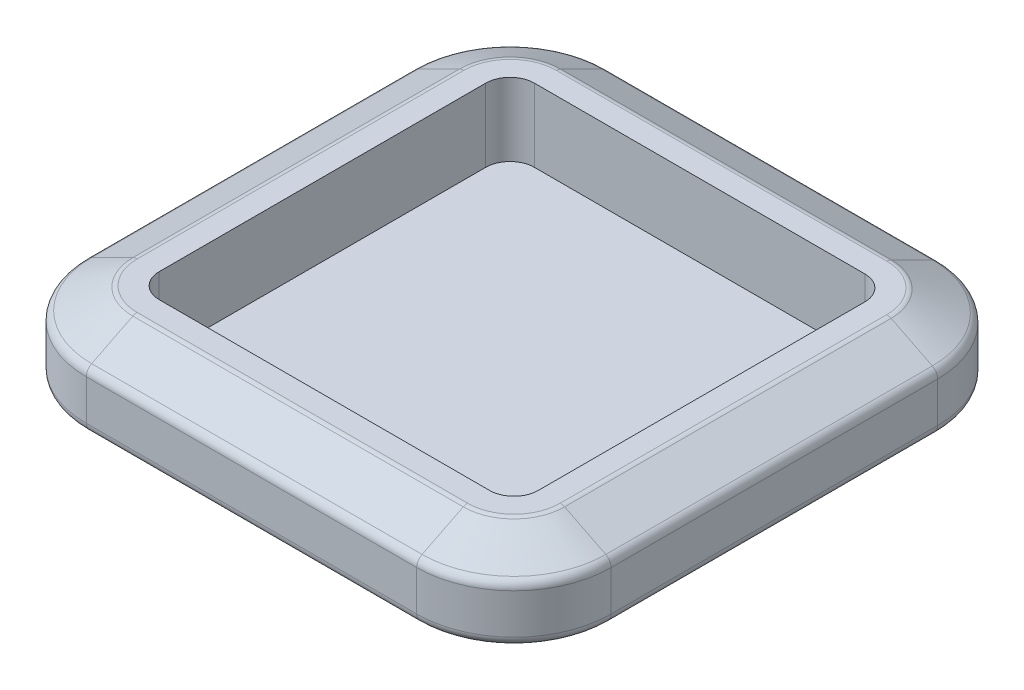
SolidWorks part; units mm, degrees
ref_plane "Front Plane" through (0, 0, 0) normal (0, 0, 1) x (1, 0, 0)
ref_plane "Top Plane" through (0, 0, 0) normal (0, 1, 0) x (1, 0, 0)
ref_plane "Right Plane" through (0, 0, 0) normal (1, 0, 0) x (0, 0, -1)
sketch "Sketch3" plane through (0, 0, 0) normal (0, 1, 0) x (1, 0, 0)
  line L0 (76.5438, 73.5629) -> (76.5438, 2.863)
  line L1 (73.5438, -0.137) -> (2.8437, -0.137)
  line L2 (-0.1563, 2.863) -> (-0.1563, 73.5629)
  line L3 (2.8437, 76.5629) -> (73.5438, 76.5629)
  line L4 (16.6192, 59.7877) -> (16.6192, 60.3885)
  line L5 (16.6192, 60.3885) -> (17.4184, 60.3885)
  line L6 (17.4184, 60.3885) -> (17.4184, 73.1876)
  line L7 (17.4184, 73.1876) -> (16.6192, 73.1876)
  line L8 (16.6192, 73.1876) -> (16.6192, 73.7884)
  line L9 (16.6192, 73.7884) -> (2.6183, 73.7884)
  line L10 (2.6183, 73.7884) -> (2.6183, 73.1876)
  line L11 (2.6183, 73.1876) -> (1.819, 73.1876)
  line L12 (1.819, 73.1876) -> (1.819, 60.3885)
  line L13 (1.819, 60.3885) -> (2.6183, 60.3885)
  line L14 (2.6183, 60.3885) -> (2.6183, 59.7877)
  line L15 (2.6183, 59.7877) -> (16.6192, 59.7877)
  line L16 (16.6192, 21.6876) -> (16.6192, 22.2884)
  line L17 (16.6192, 22.2884) -> (17.4184, 22.2884)
  line L18 (17.4184, 22.2884) -> (17.4184, 35.0876)
  line L19 (17.4184, 35.0876) -> (16.6192, 35.0876)
  line L20 (16.6192, 35.0876) -> (16.6192, 35.6884)
  line L21 (16.6192, 35.6884) -> (2.6183, 35.6884)
  line L22 (2.6183, 35.6884) -> (2.6183, 35.0876)
  line L23 (2.6183, 35.0876) -> (1.819, 35.0876)
  line L24 (1.819, 35.0876) -> (1.819, 22.2884)
  line L25 (1.819, 22.2884) -> (2.6183, 22.2884)
  line L26 (2.6183, 22.2884) -> (2.6183, 21.6876)
  line L27 (2.6183, 21.6876) -> (16.6192, 21.6876)
  line L28 (35.669, 59.7877) -> (35.669, 60.3885)
  line L29 (35.669, 60.3885) -> (36.4684, 60.3885)
  line L30 (36.4684, 60.3885) -> (36.4684, 73.1876)
  line L31 (36.4684, 73.1876) -> (35.669, 73.1876)
  line L32 (35.669, 73.1876) -> (35.669, 73.7884)
  line L33 (35.669, 73.7884) -> (21.6683, 73.7884)
  line L34 (21.6683, 73.7884) -> (21.6683, 73.1876)
  line L35 (21.6683, 73.1876) -> (20.869, 73.1876)
  line L36 (20.869, 73.1876) -> (20.869, 60.3885)
  line L37 (20.869, 60.3885) -> (21.6683, 60.3885)
  line L38 (21.6683, 60.3885) -> (21.6683, 59.7877)
  line L39 (21.6683, 59.7877) -> (35.669, 59.7877)
  line L40 (35.669, 40.7377) -> (35.669, 41.3385)
  line L41 (35.669, 41.3385) -> (36.4684, 41.3385)
  line L42 (36.4684, 41.3385) -> (36.4684, 54.1376)
  line L43 (36.4684, 54.1376) -> (35.669, 54.1376)
  line L44 (35.669, 54.1376) -> (35.669, 54.7384)
  line L45 (35.669, 54.7384) -> (21.6683, 54.7384)
  line L46 (21.6683, 54.7384) -> (21.6683, 54.1376)
  line L47 (21.6683, 54.1376) -> (20.869, 54.1376)
  line L48 (20.869, 54.1376) -> (20.869, 41.3385)
  line L49 (20.869, 41.3385) -> (21.6683, 41.3385)
  line L50 (21.6683, 41.3385) -> (21.6683, 40.7377)
  line L51 (21.6683, 40.7377) -> (35.669, 40.7377)
  line L52 (35.669, 21.6876) -> (35.669, 22.2884)
  line L53 (35.669, 22.2884) -> (36.4684, 22.2884)
  line L54 (36.4684, 22.2884) -> (36.4684, 35.0876)
  line L55 (36.4684, 35.0876) -> (35.669, 35.0876)
  line L56 (35.669, 35.0876) -> (35.669, 35.6884)
  line L57 (35.669, 35.6884) -> (21.6683, 35.6884)
  line L58 (21.6683, 35.6884) -> (21.6683, 35.0876)
  line L59 (21.6683, 35.0876) -> (20.869, 35.0876)
  line L60 (20.869, 35.0876) -> (20.869, 22.2884)
  line L61 (20.869, 22.2884) -> (21.6683, 22.2884)
  line L62 (21.6683, 22.2884) -> (21.6683, 21.6876)
  line L63 (21.6683, 21.6876) -> (35.669, 21.6876)
  line L64 (54.719, 59.7877) -> (54.719, 60.3885)
  line L65 (54.719, 60.3885) -> (55.5184, 60.3885)
  line L66 (55.5184, 60.3885) -> (55.5184, 73.1876)
  line L67 (55.5184, 73.1876) -> (54.719, 73.1876)
  line L68 (54.719, 73.1876) -> (54.719, 73.7884)
  line L69 (54.719, 73.7884) -> (40.7183, 73.7884)
  line L70 (40.7183, 73.7884) -> (40.7183, 73.1876)
  line L71 (40.7183, 73.1876) -> (39.9189, 73.1876)
  line L72 (39.9189, 73.1876) -> (39.9189, 60.3885)
  line L73 (39.9189, 60.3885) -> (40.7183, 60.3885)
  line L74 (40.7183, 60.3885) -> (40.7183, 59.7877)
  line L75 (40.7183, 59.7877) -> (54.719, 59.7877)
  line L76 (54.719, 40.7377) -> (54.719, 41.3385)
  line L77 (54.719, 41.3385) -> (55.5184, 41.3385)
  line L78 (55.5184, 41.3385) -> (55.5184, 54.1376)
  line L79 (55.5184, 54.1376) -> (54.719, 54.1376)
  line L80 (54.719, 54.1376) -> (54.719, 54.7384)
  line L81 (54.719, 54.7384) -> (40.7183, 54.7384)
  line L82 (40.7183, 54.7384) -> (40.7183, 54.1376)
  line L83 (40.7183, 54.1376) -> (39.9189, 54.1376)
  line L84 (39.9189, 54.1376) -> (39.9189, 41.3385)
  line L85 (39.9189, 41.3385) -> (40.7183, 41.3385)
  line L86 (40.7183, 41.3385) -> (40.7183, 40.7377)
  line L87 (40.7183, 40.7377) -> (54.719, 40.7377)
  line L88 (54.719, 21.6876) -> (54.719, 22.2884)
  line L89 (54.719, 22.2884) -> (55.5184, 22.2884)
  line L90 (55.5184, 22.2884) -> (55.5184, 35.0876)
  line L91 (55.5184, 35.0876) -> (54.719, 35.0876)
  line L92 (54.719, 35.0876) -> (54.719, 35.6884)
  line L93 (54.719, 35.6884) -> (40.7183, 35.6884)
  line L94 (40.7183, 35.6884) -> (40.7183, 35.0876)
  line L95 (40.7183, 35.0876) -> (39.9189, 35.0876)
  line L96 (39.9189, 35.0876) -> (39.9189, 22.2884)
  line L97 (39.9189, 22.2884) -> (40.7183, 22.2884)
  line L98 (40.7183, 22.2884) -> (40.7183, 21.6876)
  line L99 (40.7183, 21.6876) -> (54.719, 21.6876)
  line L100 (54.719, 2.6376) -> (54.719, 3.2384)
  line L101 (54.719, 3.2384) -> (55.5184, 3.2384)
  line L102 (55.5184, 3.2384) -> (55.5184, 16.0376)
  line L103 (55.5184, 16.0376) -> (54.719, 16.0376)
  line L104 (54.719, 16.0376) -> (54.719, 16.6384)
  line L105 (54.719, 16.6384) -> (40.7183, 16.6384)
  line L106 (40.7183, 16.6384) -> (40.7183, 16.0376)
  line L107 (40.7183, 16.0376) -> (39.9189, 16.0376)
  line L108 (39.9189, 16.0376) -> (39.9189, 3.2384)
  line L109 (39.9189, 3.2384) -> (40.7183, 3.2384)
  line L110 (40.7183, 3.2384) -> (40.7183, 2.6376)
  line L111 (40.7183, 2.6376) -> (54.719, 2.6376)
  line L112 (4.8812, 17.3884) -> (4.8812, 19.1629)
  line L113 (3.4438, 17.0648) -> (3.4438, 16.6384)
  line L114 (3.4438, 16.6384) -> (2.6177, 16.6384)
  line L115 (2.6177, 16.6384) -> (2.6177, 16.0374)
  line L116 (2.6177, 16.0374) -> (1.8187, 16.0374)
  line L117 (1.8187, 16.0374) -> (1.8187, 3.2386)
  line L118 (1.8187, 3.2386) -> (2.6177, 3.2386)
  line L119 (2.6177, 3.2386) -> (2.6177, 2.6376)
  line L120 (2.6177, 2.6376) -> (35.6687, 2.6376)
  line L121 (35.6687, 2.6376) -> (35.6687, 3.2386)
  line L122 (35.6687, 3.2386) -> (36.4677, 3.2386)
  line L123 (36.4677, 3.2386) -> (36.4677, 16.0374)
  line L124 (36.4677, 16.0374) -> (35.6687, 16.0374)
  line L125 (35.6687, 16.0374) -> (35.6687, 16.6384)
  line L126 (35.6687, 16.6384) -> (34.8436, 16.6384)
  line L127 (34.8436, 16.6384) -> (34.8436, 17.3884)
  line L128 (34.8436, 17.3884) -> (27.3432, 17.3884)
  line L129 (27.3432, 17.3884) -> (27.3432, 16.6384)
  line L130 (27.3432, 16.6384) -> (10.9442, 16.6384)
  line L131 (10.9442, 16.6384) -> (10.9442, 17.3884)
  line L132 (10.9442, 17.3884) -> (4.8812, 17.3884)
  line L133 (3.6353, 54.7384) -> (3.6353, 55.0694)
  line L134 (2.6183, 54.8329) -> (2.6183, 54.7384)
  line L135 (2.6183, 54.7384) -> (2.6183, 54.1376)
  line L136 (2.6183, 54.1376) -> (1.819, 54.1376)
  line L137 (1.819, 54.1376) -> (1.819, 41.3385)
  line L138 (1.819, 41.3385) -> (2.6183, 41.3385)
  line L139 (2.6183, 41.3385) -> (2.6183, 40.7377)
  line L140 (2.6183, 40.7377) -> (16.6192, 40.7377)
  line L141 (16.6192, 40.7377) -> (16.6192, 41.3385)
  line L142 (16.6192, 41.3385) -> (17.4184, 41.3385)
  line L143 (17.4184, 41.3385) -> (17.4184, 54.1376)
  line L144 (17.4184, 54.1376) -> (16.6192, 54.1376)
  line L145 (16.6192, 54.1376) -> (16.6192, 54.7384)
  line L146 (16.6192, 54.7384) -> (3.6353, 54.7384)
  line L147 (59.0183, 27.3624) -> (59.7683, 27.3624)
  line L148 (59.7683, 27.3624) -> (59.7683, 10.9635)
  line L149 (59.7683, 10.9635) -> (59.0183, 10.9635)
  line L150 (59.0183, 10.9635) -> (59.0183, 3.4631)
  line L151 (59.0183, 3.4631) -> (59.7683, 3.4631)
  line L152 (59.7683, 3.4631) -> (59.7683, 2.6379)
  line L153 (59.7683, 2.6379) -> (60.3693, 2.6379)
  line L154 (60.3693, 2.6379) -> (60.3693, 1.8389)
  line L155 (60.3693, 1.8389) -> (73.168, 1.8389)
  line L156 (73.168, 1.8389) -> (73.168, 2.6379)
  line L157 (73.168, 2.6379) -> (73.769, 2.6379)
  line L158 (73.769, 2.6379) -> (73.769, 35.9355)
  line L159 (73.769, 40.4103) -> (73.769, 73.7889)
  line L160 (73.769, 73.7889) -> (73.168, 73.7889)
  line L161 (73.168, 73.7889) -> (73.168, 74.5879)
  line L162 (73.168, 74.5879) -> (60.3693, 74.5879)
  line L163 (60.3693, 74.5879) -> (60.3693, 73.7889)
  line L164 (60.3693, 73.7889) -> (59.7683, 73.7889)
  line L165 (59.7683, 73.7889) -> (59.7683, 72.9628)
  line L166 (59.7683, 72.9628) -> (59.0183, 72.9628)
  line L167 (59.0183, 72.9628) -> (59.0183, 65.4626)
  line L168 (59.0183, 65.4626) -> (59.7683, 65.4626)
  line L169 (59.7683, 65.4626) -> (59.7683, 49.0635)
  line L170 (59.7683, 49.0635) -> (59.0183, 49.0635)
  line L171 (59.0183, 49.0635) -> (59.0183, 41.5633)
  line L172 (59.0183, 41.5633) -> (59.7683, 41.5633)
  line L173 (59.7683, 41.5633) -> (59.7683, 40.7379)
  line L174 (59.7683, 40.7379) -> (60.3693, 40.7379)
  line L175 (60.3693, 40.7379) -> (60.3693, 39.9389)
  line L176 (60.3693, 39.9389) -> (71.2821, 39.9389)
  line L177 (71.2821, 39.9389) -> (71.2821, 38.236)
  line L178 (71.2821, 38.1098) -> (71.2821, 36.4879)
  line L179 (71.2821, 36.4879) -> (60.3693, 36.4879)
  line L180 (60.3693, 36.4879) -> (60.3693, 35.6889)
  line L181 (60.3693, 35.6889) -> (59.7683, 35.6889)
  line L182 (59.7683, 35.6889) -> (59.7683, 34.8629)
  line L183 (59.7683, 34.8629) -> (59.0183, 34.8629)
  line L184 (59.0183, 34.8629) -> (59.0183, 27.3624)
  arc A0 (76.5438, 73.5629) -> (73.5438, 76.5629) centre (73.5438, 73.5629) ccw
  arc A1 (73.5438, -0.137) -> (76.5438, 2.863) centre (73.5438, 2.863) ccw
  arc A2 (-0.1563, 2.863) -> (2.8437, -0.137) centre (2.8437, 2.863) ccw
  arc A3 (2.8437, 76.5629) -> (-0.1563, 73.5629) centre (2.8437, 73.5629) ccw
  arc A4 (4.8812, 19.1629) -> (3.4438, 17.0648) centre (2.6312, 19.1629) ccw
  arc A5 (3.6353, 55.0694) -> (2.6183, 54.8329) centre (2.6312, 57.0829) ccw
  arc A6 (73.769, 35.9355) -> (73.769, 40.4103) centre (73.5312, 38.1729) ccw
  arc A7 (71.2821, 38.236) -> (71.2821, 38.1098) centre (73.5312, 38.1729) ccw
  circle A8 centre (57.1912, 19.0529) radius 2.25
  circle A9 centre (38.1412, 38.1029) radius 2.25
sketch "Sketch4" plane through (0, 0, 0) normal (0, 1, 0) x (1, 0, 0)
  line L0 (16.6192, 73.7884) -> (2.6183, 73.7884) construction
  line L1 (-1.181, 76.7884) -> (76.769, 76.7884)
  line L2 (-1.181, 76.7884) -> (-1.181, -0.3624)
  line L3 (-1.181, -0.3624) -> (76.769, -0.3624)
  line L4 (76.769, 76.7884) -> (76.769, -0.3624)
  line L5 (-16.181, 91.7884) -> (91.769, 91.7884)
  line L6 (1.819, 73.1876) -> (1.819, 60.3885) construction
  line L7 (73.769, 40.4103) -> (73.769, 73.7889) construction
  line L8 (2.6177, 2.6376) -> (35.6687, 2.6376) construction
  line L9 (73.5438, -0.137) -> (2.8437, -0.137) construction
  line L10 (91.769, 91.7884) -> (91.769, -15.3624)
  line L11 (-16.181, -15.3624) -> (91.769, -15.3624)
  line L12 (-16.181, 91.7884) -> (-16.181, -15.3624)
  dimension "D1" = 3
  dimension "D2" = 3
  dimension "D3" = 3
  dimension "D4" = 3
  dimension "D5" = 0.2254
  dimension "D6" = 15
  dimension "D7" = 107.1508
sketch3d "3DSketch1"
  line L1 (91.769, 0, -91.7884) -> (91.769, 0, 15.3624) construction
sketch "Sketch5" plane through (91.769, 0, 0) normal (-1, 0, 0) x (0, 0, 1)
  line L0 (15.3616, 0) -> (-91.7884, 0)
  line L1 (-91.7884, 0) -> (15.3624, 0) construction
  line L2 (-91.7884, 0) -> (-91.7884, -18.5)
  line L3 (15.3616, 0) -> (15.3616, -18.5)
  line L4 (15.3616, -18.5) -> (-91.7884, -18.5)
  dimension "D1" = 18.5
  dimension "D2" = 18.5
  dimension "D3" = 107.15
extrude "Boss-Extrude1" add sketch "Sketch5" along normal up to vertex (107.95 mm away) up to point (-16.181, 0, 15.3624)
extrude "Cut-Extrude1" cut sketch "Sketch4" against normal blind 7.5 contours L4 L1 L2 L3 region at (37.794, 0, -38.213)
fillet "Fillet1" radius 5 4 edges at (-1.181, -3.75, 0.3624) (76.769, -3.75, 0.3624) (76.769, -3.75, -76.7884) (-1.181, -3.75, -76.7884)
fillet "Fillet3" radius 20 4 edges at (91.769, -9.25, -91.7884) (91.769, -9.25, 15.3616) (-16.181, -9.25, 15.3616) (-16.181, -9.25, -91.7884)
chamfer "Chamfer1" distance 10 distance2 5 8 edges at (91.769, 0, -38.2134) (85.9111, 0, 9.5037) (85.9111, 0, -85.9305) (37.794, 0, 15.3616) (37.794, 0, -91.7884) (-10.3231, 0, 9.5037) (-10.3231, 0, -85.9305) (-16.181, 0, -38.2134) first distance on face at (37.794, 0, -38.2134)
sketch "Sketch6" plane through (0, -18.5, 0) normal (0, -1, 0) x (1, 0, 0)
  line L4 (3.819, -91.7884) -> (71.769, -91.7884) construction
  line L5 (91.769, -71.7884) -> (91.769, -4.6384) construction
  line L6 (-16.181, -71.7884) -> (-16.181, -4.6384) construction
  line L7 (3.819, 15.3616) -> (71.769, 15.3616) construction
  line L8 (3.819, -79.7884) -> (71.769, -79.7884)
  line L9 (79.769, -71.7884) -> (79.769, -4.6384)
  line L10 (71.769, 3.3616) -> (3.819, 3.3616)
  line L11 (-4.181, -4.6384) -> (-4.181, -71.7884)
  line L12 (3.819, -79.7884) -> (71.769, -79.7884)
  line L13 (79.769, -71.7884) -> (79.769, -4.6384)
  line L14 (71.769, 3.3616) -> (3.819, 3.3616)
  line L15 (-4.181, -4.6384) -> (-4.181, -71.7884)
  line L16 (3.819, -91.7884) -> (71.769, -91.7884)
  line L17 (91.769, -71.7884) -> (91.769, -4.6384)
  line L18 (-16.181, -71.7884) -> (-16.181, -4.6384)
  line L19 (3.819, 15.3616) -> (71.769, 15.3616)
  arc A4 (-16.181, -71.7884) -> (3.819, -91.7884) centre (3.819, -71.7884) ccw construction
  arc A5 (71.769, -91.7884) -> (91.769, -71.7884) centre (71.769, -71.7884) ccw construction
  arc A6 (91.769, -4.6384) -> (71.769, 15.3616) centre (71.769, -4.6384) ccw construction
  arc A7 (3.819, 15.3616) -> (-16.181, -4.6384) centre (3.819, -4.6384) ccw construction
  arc A8 (71.769, -79.7884) -> (79.769, -71.7884) centre (71.769, -71.7884) ccw
  arc A9 (79.769, -4.6384) -> (71.769, 3.3616) centre (71.769, -4.6384) ccw
  arc A10 (3.819, 3.3616) -> (-4.181, -4.6384) centre (3.819, -4.6384) ccw
  arc A11 (-4.181, -71.7884) -> (3.819, -79.7884) centre (3.819, -71.7884) ccw
  arc A12 (71.769, -79.7884) -> (79.769, -71.7884) centre (71.769, -71.7884) ccw
  arc A13 (79.769, -4.6384) -> (71.769, 3.3616) centre (71.769, -4.6384) ccw
  arc A14 (3.819, 3.3616) -> (-4.181, -4.6384) centre (3.819, -4.6384) ccw
  arc A15 (-4.181, -71.7884) -> (3.819, -79.7884) centre (3.819, -71.7884) ccw
  arc A16 (-16.181, -71.7884) -> (3.819, -91.7884) centre (3.819, -71.7884) ccw
  arc A17 (71.769, -91.7884) -> (91.769, -71.7884) centre (71.769, -71.7884) ccw
  arc A18 (91.769, -4.6384) -> (71.769, 15.3616) centre (71.769, -4.6384) ccw
  arc A19 (3.819, 15.3616) -> (-16.181, -4.6384) centre (3.819, -4.6384) ccw
  dimension "D1" = 12
extrude "Cut-Extrude2" cut sketch "Sketch6" against normal blind 2
fillet "Fillet4" radius 20 8 edges at (77.4259, -16.5, 1.0185) (79.769, -16.5, -38.2134) (77.4259, -16.5, -77.4453) (37.794, -16.5, -79.7884) (-1.8378, -16.5, -77.4453) (-4.181, -16.5, -38.2134) (-1.8378, -16.5, 1.0185) (37.794, -16.5, 3.3616)
fillet "Fillet5" radius 2 24 edges at (85.9111, -5, 9.5037) (91.769, -5, -38.2134) (85.9111, -5, -85.9305) (37.794, -5, -91.7884) (-10.3231, -5, -85.9305) (-16.181, -5, -38.2134) (-10.3231, -5, 9.5037) (-3.2521, 0, 2.4327) (-6.181, 0, -38.2134) (-3.2521, 0, -78.8595) (37.794, 0, -81.7884) (78.8401, 0, -78.8595) (81.769, 0, -38.2134) (78.8401, 0, 2.4327) (37.794, -5, 15.3616) (37.794, 0, 5.3616) (-10.3231, -16.5, -85.9305) (-16.181, -16.5, -38.2134) (-10.3231, -16.5, 9.5037) (37.794, -16.5, 15.3616) (85.9111, -16.5, 9.5037) (91.769, -16.5, -38.2134) (85.9111, -16.5, -85.9305) (37.794, -16.5, -91.7884)
sketch "Sketch8" plane through (0, -7.5, 0) normal (0, 1, 0) x (1, 0, 0)
  line L4 (-1.181, 71.7884) -> (-1.181, 4.6376)
  line L5 (3.819, -0.3624) -> (71.769, -0.3624)
  line L6 (76.769, 4.6376) -> (76.769, 71.7884)
  line L7 (71.769, 76.7884) -> (3.819, 76.7884)
  line L8 (-1.181, 71.7884) -> (-1.181, 4.6376)
  line L9 (3.819, -0.3624) -> (71.769, -0.3624)
  line L10 (76.769, 4.6376) -> (76.769, 71.7884)
  line L11 (71.769, 76.7884) -> (3.819, 76.7884)
  arc A4 (-1.181, 4.6376) -> (3.819, -0.3624) centre (3.819, 4.6376) ccw
  arc A5 (71.769, -0.3624) -> (76.769, 4.6376) centre (71.769, 4.6376) ccw
  arc A6 (76.769, 71.7884) -> (71.769, 76.7884) centre (71.769, 71.7884) ccw
  arc A7 (3.819, 76.7884) -> (-1.181, 71.7884) centre (3.819, 71.7884) ccw
  arc A8 (-1.181, 4.6376) -> (3.819, -0.3624) centre (3.819, 4.6376) ccw
  arc A9 (71.769, -0.3624) -> (76.769, 4.6376) centre (71.769, 4.6376) ccw
  arc A10 (76.769, 71.7884) -> (71.769, 76.7884) centre (71.769, 71.7884) ccw
  arc A11 (3.819, 76.7884) -> (-1.181, 71.7884) centre (3.819, 71.7884) ccw
  dimension "D1" = 0
extrude "Cut-Extrude3" cut sketch "Sketch8" against normal blind 7.5
